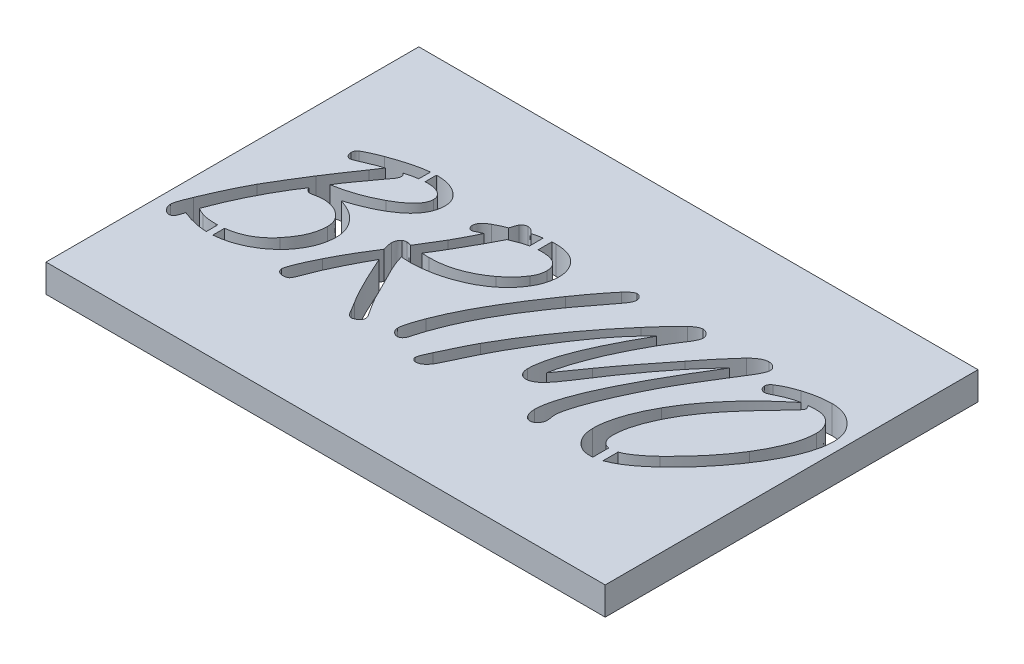
SolidWorks part; units mm, degrees
ref_plane "Front Plane" through (0, 0, 0) normal (0, 0, 1) x (1, 0, 0)
ref_plane "Top Plane" through (0, 0, 0) normal (0, 1, 0) x (1, 0, 0)
ref_plane "Right Plane" through (0, 0, 0) normal (1, 0, 0) x (0, 0, -1)
sketch "Sketch1" plane through (0, 0, 0) normal (0, 1, 0) x (1, 0, 0)
  line L1 (-15, -10) -> (15, -10)
  line L2 (-15, -10) -> (-15, 10)
  line L3 (-15, 10) -> (15, 10)
  line L4 (15, -10) -> (15, 10)
  line L5 (-15, -10) -> (15, 10) construction
  line L6 (-15, 10) -> (15, -10) construction
  point P0 (0, 0)
  dimension "D1" = 20
  dimension "D2" = 30
extrude "Boss-Extrude1" add sketch "Sketch1" along normal blind 1.5
sketch "Sketch2" plane through (0, 1.5, 0) normal (0, 1, 0) x (1, 0, 0)
  line L0 (12.5358, 3.7992) -> (12.0968, 3.7801)
  spline S0 degree 3 poles (-9.9324, 0.7721) (-9.7349, 0.705) (-9.3793, 0.5645) (-9.0629, 0.3483) (-8.9399, 0.2281) knots 0 0 0 0 0.54938 1 1 1 1
  spline S1 degree 3 poles (-8.9399, 0.2281) (-8.8499, 0.139) (-8.7235, -0.0008) (-8.5891, -0.2075) (-8.5077, -0.366) (-8.4446, -0.5298) (-8.3855, -0.7576) (-8.3678, -0.934) (-8.3674, -1.0525) knots 0 0 0 0 0.263598 0.389786 0.511629 0.633452 0.753743 1 1 1 1
  spline S2 degree 3 poles (-8.3674, -1.0525) (-8.3679, -1.1976) (-8.3862, -1.4147) (-8.4444, -1.6988) (-8.5079, -1.9082) (-8.5913, -2.1139) (-8.7218, -2.3919) (-8.8493, -2.5878) (-8.9418, -2.7149) knots 0 0 0 0 0.24321 0.364144 0.485641 0.609656 0.73611 1 1 1 1
  spline S3 degree 3 poles (-8.9418, -2.7149) (-9.1183, -2.9551) (-9.5377, -3.392) (-10.0436, -3.7249) (-10.316, -3.8601) knots 0 0 0 0 0.494771 1 1 1 1
  spline S4 degree 3 poles (-10.316, -3.8601) (-10.5882, -3.9961) (-11.1539, -4.2113) (-11.7551, -4.2809) (-12.051, -4.2819) knots 0 0 0 0 0.507133 1 1 1 1
  spline S5 degree 3 poles (-12.051, -4.2819) (-12.2925, -4.2818) (-12.803, -4.2161) (-13.2931, -4.0595) (-13.5435, -3.9555) knots 0 0 0 0 0.470723 1 1 1 1
  spline S6 degree 3 poles (-13.5435, -3.9555) (-13.5635, -4.0027) (-13.584, -4.0814) (-13.614, -4.1569) (-13.6198, -4.1865) knots 0 0 0 0 0.630096 1 1 1 1
  spline S7 degree 3 poles (-13.6198, -4.1865) (-13.6445, -4.2663) (-13.7016, -4.4114) (-13.838, -4.4919) (-13.9042, -4.488) knots 0 0 0 0 0.574548 1 1 1 1
  spline S8 degree 3 poles (-13.9042, -4.488) (-13.9704, -4.4895) (-14.1096, -4.4451) (-14.2083, -4.3383) (-14.2497, -4.2762) knots 0 0 0 0 0.465807 1 1 1 1
  spline S9 degree 2 poles (-14.2497, -4.2762) (-14.347, -4.1407) (-14.3528, -3.9746) knots 0 0 0 1 1 1
  spline S10 degree 3 poles (-14.3528, -3.9746) (-14.354, -3.926) (-14.3377, -3.8471) (-14.3104, -3.7313) (-14.275, -3.6224) (-14.2328, -3.497) (-14.1611, -3.2981) (-14.0922, -3.145) (-14.0493, -3.0356) knots 0 0 0 0 0.146035 0.243208 0.360183 0.492362 0.644092 1 1 1 1
  spline S11 degree 3 poles (-14.0493, -3.0356) (-13.951, -2.8027) (-13.8059, -2.4631) (-13.6103, -2.026) (-13.4703, -1.7282) (-13.3368, -1.4495) (-13.1732, -1.1148) (-13.046, -0.8771) (-12.9614, -0.7262) knots 0 0 0 0 0.296924 0.433728 0.562437 0.683432 0.796727 1 1 1 1
  spline S12 degree 3 poles (-12.9614, -0.7262) (-12.9019, -0.619) (-12.8008, -0.4453) (-12.6526, -0.1946) (-12.5099, 0.0354) (-12.353, 0.2979) (-12.1005, 0.7031) (-11.9023, 1.022) (-11.7628, 1.2435) knots 0 0 0 0 0.159441 0.261503 0.3789 0.511482 0.659407 1 1 1 1
  spline S13 degree 3 poles (-11.7628, 1.2435) (-11.6906, 1.3584) (-11.5739, 1.5364) (-11.4105, 1.7825) (-11.2727, 1.9894) (-11.1242, 2.2105) (-10.9038, 2.5333) (-10.7304, 2.7805) (-10.6138, 2.9517) knots 0 0 0 0 0.197743 0.310104 0.430435 0.560023 0.698104 1 1 1 1
  spline S14 degree 2 poles (-10.6138, 2.9517) (-10.4349, 3.2066) (-10.2702, 3.4709) knots 0 0 0 1 1 1
  spline S15 degree 3 poles (-10.2702, 3.4709) (-10.4018, 3.4327) (-10.6913, 3.3256) (-10.9761, 3.2067) (-11.1329, 3.1369) knots 0 0 0 0 0.443553 1 1 1 1
  spline S16 degree 3 poles (-11.1329, 3.1369) (-11.2484, 3.0843) (-11.4199, 3.0178) (-11.5936, 2.9522) (-11.6521, 2.946) knots 0 0 0 0 0.684268 1 1 1 1
  spline S17 degree 2 poles (-11.6521, 2.946) (-11.7629, 2.9529) (-11.8315, 3.0414) knots 0 0 0 1 1 1
  spline S18 degree 2 poles (-11.8315, 3.0414) (-11.9085, 3.1408) (-11.9078, 3.2666) knots 0 0 0 1 1 1
  spline S19 degree 3 poles (-11.9078, 3.2666) (-11.9068, 3.324) (-11.8898, 3.4402) (-11.8082, 3.5249) (-11.7628, 3.5529) knots 0 0 0 0 0.520839 1 1 1 1
  spline S20 degree 3 poles (-11.7628, 3.5529) (-11.6453, 3.6264) (-11.3377, 3.7844) (-11.0151, 3.9087) (-10.8218, 3.9824) knots 0 0 0 0 0.400792 1 1 1 1
  spline S21 degree 3 poles (-10.8218, 3.9824) (-10.5989, 4.0625) (-10.2751, 4.1829) (-9.8455, 4.3037) (-9.5525, 4.3827) (-9.2749, 4.4389) (-8.9413, 4.4946) (-8.6975, 4.5133) (-8.541, 4.513) knots 0 0 0 0 0.302191 0.439787 0.568842 0.688942 0.800686 1 1 1 1
  spline S22 degree 3 poles (-8.541, 4.513) (-8.3188, 4.5116) (-7.8963, 4.4723) (-7.5122, 4.2903) (-7.3558, 4.1732) knots 0 0 0 0 0.533748 1 1 1 1
  spline S23 degree 3 poles (-7.3558, 4.1732) (-7.2849, 4.1193) (-7.1843, 4.0329) (-7.0784, 3.8969) (-7.012, 3.7936) (-6.9619, 3.6837) (-6.9161, 3.528) (-6.9016, 3.4061) (-6.9015, 3.3239) knots 0 0 0 0 0.267458 0.393647 0.515248 0.634635 0.754006 1 1 1 1
  spline S24 degree 3 poles (-6.9015, 3.3239) (-6.9019, 3.1512) (-6.943, 2.8903) (-7.0819, 2.5662) (-7.2282, 2.3321) (-7.416, 2.108) (-7.7327, 1.8087) (-8.0162, 1.6207) (-8.2166, 1.5012) knots 0 0 0 0 0.219659 0.331396 0.446659 0.569712 0.702581 1 1 1 1
  spline S25 degree 3 poles (-8.2166, 1.5012) (-8.4812, 1.3441) (-9.0423, 1.0711) (-9.6282, 0.8568) (-9.9324, 0.7721) knots 0 0 0 0 0.49355 1 1 1 1
  spline S26 degree 3 poles (-10.9688, 1.2149) (-10.5802, 1.2808) (-9.8113, 1.4731) (-9.0867, 1.7947) (-8.7395, 1.9841) knots 0 0 0 0 0.499167 1 1 1 1
  spline S27 degree 3 poles (-8.7395, 1.9841) (-8.5538, 2.0831) (-8.2974, 2.2401) (-7.9959, 2.472) (-7.8223, 2.6395) (-7.6837, 2.8047) (-7.5579, 3.021) (-7.511, 3.1958) (-7.5123, 3.3105) knots 0 0 0 0 0.334645 0.477362 0.604033 0.717668 0.819211 1 1 1 1
  spline S28 degree 3 poles (-7.5123, 3.3105) (-7.5127, 3.4056) (-7.5684, 3.6137) (-7.7453, 3.7373) (-7.8368, 3.7877) knots 0 0 0 0 0.472721 1 1 1 1
  spline S29 degree 3 poles (-7.8368, 3.7877) (-7.9164, 3.8292) (-8.1115, 3.8909) (-8.3156, 3.9005) (-8.4284, 3.9022) knots 0 0 0 0 0.441874 1 1 1 1
  spline S30 degree 3 poles (-8.4284, 3.9022) (-8.6058, 3.9032) (-8.9873, 3.8621) (-9.3598, 3.7713) (-9.5564, 3.7114) knots 0 0 0 0 0.462913 1 1 1 1
  spline S31 degree 3 poles (-9.5564, 3.7114) (-9.5203, 3.6881) (-9.46, 3.629) (-9.4355, 3.548) (-9.4362, 3.509) knots 0 0 0 0 0.526905 1 1 1 1
  spline S32 degree 3 poles (-9.4362, 3.509) (-9.44, 3.4406) (-9.4955, 3.2764) (-9.6073, 3.1445) (-9.669, 3.0643) knots 0 0 0 0 0.400176 1 1 1 1
  spline S33 degree 3 poles (-9.669, 3.0643) (-9.7058, 3.0181) (-9.7984, 2.893) (-9.8901, 2.7673) (-9.9458, 2.6883) knots 0 0 0 0 0.37937 1 1 1 1
  spline S34 degree 3 poles (-9.9458, 2.6883) (-9.9661, 2.6605) (-9.9966, 2.6094) (-10.0499, 2.5374) (-10.1042, 2.4642) (-10.166, 2.3768) (-10.2692, 2.2363) (-10.3521, 2.1256) (-10.4096, 2.047) knots 0 0 0 0 0.130417 0.225441 0.339258 0.475767 0.631066 1 1 1 1
  spline S35 degree 3 poles (-10.4096, 2.047) (-10.5229, 1.8942) (-10.718, 1.6225) (-10.8969, 1.3398) (-10.9688, 1.2149) knots 0 0 0 0 0.569145 1 1 1 1
  spline S36 degree 3 poles (-13.3755, -3.3963) (-13.309, -3.4356) (-13.1926, -3.4898) (-13.0768, -3.5456) (-13.0282, -3.5624) knots 0 0 0 0 0.600478 1 1 1 1
  spline S37 degree 3 poles (-13.0282, -3.5624) (-12.9152, -3.6025) (-12.6518, -3.6608) (-12.3825, -3.6684) (-12.2342, -3.6712) knots 0 0 0 0 0.446321 1 1 1 1
  spline S38 degree 3 poles (-12.2342, -3.6712) (-11.9986, -3.6689) (-11.6488, -3.6432) (-11.2057, -3.5245) (-10.8972, -3.4069) (-10.6077, -3.2542) (-10.2422, -3.003) (-10.0039, -2.7645) (-9.8599, -2.5909) knots 0 0 0 0 0.262261 0.386546 0.508478 0.628294 0.749249 1 1 1 1
  spline S39 degree 3 poles (-9.8599, -2.5909) (-9.7394, -2.4469) (-9.5768, -2.2248) (-9.3945, -1.9167) (-9.2873, -1.6911) (-9.2043, -1.4662) (-9.126, -1.171) (-9.0988, -0.9457) (-9.1003, -0.7968) knots 0 0 0 0 0.283179 0.414403 0.539791 0.659455 0.77565 1 1 1 1
  spline S40 degree 3 poles (-9.1003, -0.7968) (-9.1009, -0.7011) (-9.117, -0.5583) (-9.179, -0.3799) (-9.2437, -0.2561) (-9.3234, -0.1386) (-9.4623, 0.0088) (-9.5882, 0.1003) (-9.6786, 0.1556) knots 0 0 0 0 0.245661 0.3649 0.482429 0.60331 0.728041 1 1 1 1
  spline S41 degree 3 poles (-9.6786, 0.1556) (-9.793, 0.2259) (-10.0547, 0.3291) (-10.3339, 0.3592) (-10.4783, 0.3598) knots 0 0 0 0 0.481057 1 1 1 1
  spline S42 degree 3 poles (-10.4783, 0.3598) (-10.5505, 0.3601) (-10.7236, 0.3426) (-10.894, 0.3084) (-10.9936, 0.2892) knots 0 0 0 0 0.415623 1 1 1 1
  spline S43 degree 2 poles (-10.9936, 0.2892) (-11.056, 0.2769) (-11.1196, 0.2759) knots 0 0 0 1 1 1
  spline S44 degree 3 poles (-11.1196, 0.2759) (-11.1774, 0.2719) (-11.2946, 0.3314) (-11.3691, 0.4367) (-11.3982, 0.5011) knots 0 0 0 0 0.439946 1 1 1 1
  spline S45 degree 3 poles (-11.3982, 0.5011) (-11.4981, 0.3605) (-11.6471, 0.1386) (-11.8397, -0.1762) (-11.9935, -0.4395) (-12.1545, -0.721) (-12.3754, -1.1358) (-12.5428, -1.4565) (-12.6522, -1.6786) knots 0 0 0 0 0.205495 0.318511 0.439849 0.568893 0.70494 1 1 1 1
  spline S46 degree 3 poles (-12.6522, -1.6786) (-12.7776, -1.9379) (-13.0389, -2.5023) (-13.2589, -3.0841) (-13.3755, -3.3963) knots 0 0 0 0 0.463574 1 1 1 1
  spline S47 degree 3 poles (-6.1877, -0.9457) (-6.33, -1.203) (-6.533, -1.5796) (-6.7863, -2.0714) (-6.9521, -2.4088) (-7.1013, -2.7256) (-7.2703, -3.1047) (-7.3829, -3.3812) (-7.4474, -3.5605) knots 0 0 0 0 0.303657 0.44176 0.571338 0.69184 0.803309 1 1 1 1
  spline S48 degree 3 poles (-7.4474, -3.5605) (-7.4779, -3.6449) (-7.5233, -3.7634) (-7.5816, -3.9106) (-7.6216, -3.9966) (-7.6517, -4.0697) (-7.688, -4.1338) (-7.7134, -4.1736) (-7.7318, -4.1922) knots 0 0 0 0 0.387425 0.547466 0.682625 0.796883 0.887789 1 1 1 1
  spline S49 degree 3 poles (-7.7318, -4.1922) (-7.7648, -4.2273) (-7.8637, -4.2692) (-7.9688, -4.283) (-8.0276, -4.2819) knots 0 0 0 0 0.444412 1 1 1 1
  spline S50 degree 3 poles (-8.0276, -4.2819) (-8.0774, -4.2829) (-8.1739, -4.2688) (-8.2553, -4.2149) (-8.2853, -4.1808) knots 0 0 0 0 0.525178 1 1 1 1
  spline S51 degree 2 poles (-8.2853, -4.1808) (-8.3613, -4.0988) (-8.3674, -3.988) knots 0 0 0 1 1 1
  spline S52 degree 3 poles (-8.3674, -3.988) (-8.3664, -3.9165) (-8.334, -3.7965) (-8.2754, -3.6182) (-8.2053, -3.4376) (-8.1152, -3.2267) (-7.9604, -2.882) (-7.8283, -2.6113) (-7.7337, -2.421) knots 0 0 0 0 0.125195 0.21875 0.331978 0.467572 0.624161 1 1 1 1
  spline S53 degree 3 poles (-7.7337, -2.421) (-7.5709, -2.0885) (-7.1843, -1.3876) (-6.7681, -0.704) (-6.5351, -0.3425) knots 0 0 0 0 0.462548 1 1 1 1
  spline S54 degree 3 poles (-6.5351, -0.3425) (-6.5647, -0.2466) (-6.6025, -0.0789) (-6.6314, 0.091) (-6.6305, 0.1632) knots 0 0 0 0 0.582415 1 1 1 1
  spline S55 degree 3 poles (-6.6305, 0.1632) (-6.6312, 0.239) (-6.602, 0.3888) (-6.5089, 0.51) (-6.4511, 0.5545) knots 0 0 0 0 0.510937 1 1 1 1
  spline S56 degree 2 poles (-6.4511, 0.5545) (-6.3635, 0.6197) (-6.2545, 0.6194) knots 0 0 0 1 1 1
  spline S57 degree 2 poles (-6.2545, 0.6194) (-6.1222, 0.6133) (-6.0026, 0.5545) knots 0 0 0 1 1 1
  spline S58 degree 3 poles (-6.0026, 0.5545) (-5.9746, 0.602) (-5.9223, 0.6861) (-5.8419, 0.8187) (-5.755, 0.9597) (-5.651, 1.1298) (-5.4764, 1.4113) (-5.3418, 1.6403) (-5.241, 1.7989) knots 0 0 0 0 0.113303 0.203721 0.318822 0.453891 0.613642 1 1 1 1
  spline S59 degree 3 poles (-5.241, 1.7989) (-5.1557, 1.9625) (-5.0255, 2.1882) (-4.8785, 2.4791) (-4.7852, 2.6509) (-4.7136, 2.7971) (-4.6454, 2.9327) (-4.6058, 3.0222) (-4.5883, 3.0739) knots 0 0 0 0 0.386157 0.545202 0.682224 0.79539 0.885924 1 1 1 1
  spline S60 degree 2 poles (-4.5883, 3.0739) (-4.7393, 3.0137) (-4.8822, 2.9365) knots 0 0 0 1 1 1
  spline S61 degree 2 poles (-4.8822, 2.9365) (-4.9704, 2.8893) (-5.0693, 2.8792) knots 0 0 0 1 1 1
  spline S62 degree 2 poles (-5.0693, 2.8792) (-5.168, 2.885) (-5.2201, 2.9708) knots 0 0 0 1 1 1
  spline S63 degree 2 poles (-5.2201, 2.9708) (-5.2693, 3.0444) (-5.2678, 3.133) knots 0 0 0 1 1 1
  spline S64 degree 3 poles (-5.2678, 3.133) (-5.2665, 3.1866) (-5.2538, 3.269) (-5.2036, 3.3683) (-5.1534, 3.442) (-5.0873, 3.5127) (-4.9756, 3.6078) (-4.877, 3.6671) (-4.8078, 3.7056) knots 0 0 0 0 0.209364 0.316672 0.430565 0.55486 0.691692 1 1 1 1
  spline S65 degree 2 poles (-4.8078, 3.7056) (-4.5026, 3.8755) (-4.176, 3.9996) knots 0 0 0 1 1 1
  spline S66 degree 3 poles (-4.176, 3.9996) (-4.1545, 4.0862) (-4.1044, 4.2198) (-4.059, 4.3557) (-4.031, 4.4023) knots 0 0 0 0 0.62241 1 1 1 1
  spline S67 degree 3 poles (-4.031, 4.4023) (-4.0022, 4.456) (-3.9133, 4.553) (-3.7844, 4.5777) (-3.7218, 4.5779) knots 0 0 0 0 0.492095 1 1 1 1
  spline S68 degree 3 poles (-3.7218, 4.5779) (-3.6454, 4.5787) (-3.4805, 4.5304) (-3.3677, 4.4011) (-3.3172, 4.3297) knots 0 0 0 0 0.46182 1 1 1 1
  spline S69 degree 3 poles (-3.3172, 4.3297) (-3.1152, 4.387) (-2.7292, 4.4766) (-2.3345, 4.5129) (-2.1491, 4.513) knots 0 0 0 0 0.531298 1 1 1 1
  spline S70 degree 3 poles (-2.1491, 4.513) (-2.0237, 4.5156) (-1.8419, 4.5002) (-1.6081, 4.4575) (-1.4508, 4.4089) (-1.3035, 4.3513) (-1.1285, 4.2495) (-1.0079, 4.1597) (-0.9409, 4.0854) knots 0 0 0 0 0.284878 0.414697 0.540253 0.65914 0.773942 1 1 1 1
  spline S71 degree 3 poles (-0.9409, 4.0854) (-0.8145, 3.9556) (-0.61, 3.6428) (-0.55, 3.2744) (-0.5497, 3.0911) knots 0 0 0 0 0.496609 1 1 1 1
  spline S72 degree 3 poles (-0.5497, 3.0911) (-0.5525, 2.9332) (-0.5727, 2.6947) (-0.6598, 2.3879) (-0.7453, 2.159) (-0.8583, 1.934) (-1.0486, 1.6339) (-1.2173, 1.4207) (-1.3456, 1.2874) knots 0 0 0 0 0.234943 0.352534 0.472741 0.597393 0.72559 1 1 1 1
  spline S73 degree 3 poles (-1.3456, 1.2874) (-1.4703, 1.1527) (-1.6774, 0.9674) (-1.9746, 0.7414) (-2.2174, 0.5851) (-2.474, 0.4376) (-2.8456, 0.2582) (-3.1362, 0.1396) (-3.3382, 0.0735) knots 0 0 0 0 0.233458 0.353169 0.474931 0.60081 0.729765 1 1 1 1
  spline S74 degree 3 poles (-3.3382, 0.0735) (-3.647, -0.0308) (-4.2677, -0.1928) (-4.9067, -0.2503) (-5.2201, -0.2509) knots 0 0 0 0 0.509986 1 1 1 1
  spline S75 degree 3 poles (-5.2201, -0.2509) (-5.2869, -0.25) (-5.4479, -0.2448) (-5.6088, -0.2367) (-5.7029, -0.2318) knots 0 0 0 0 0.414852 1 1 1 1
  spline S76 degree 2 poles (-5.7029, -0.2318) (-5.5875, -0.64) (-5.4071, -1.0239) knots 0 0 0 1 1 1
  spline S77 degree 3 poles (-5.4071, -1.0239) (-5.3475, -1.1433) (-5.2513, -1.3296) (-5.1198, -1.5906) (-5.0088, -1.8128) (-4.8896, -2.0525) (-4.7088, -2.4052) (-4.5738, -2.6807) (-4.4795, -2.8695) knots 0 0 0 0 0.193804 0.304548 0.424382 0.554546 0.69339 1 1 1 1
  spline S78 degree 3 poles (-4.4795, -2.8695) (-4.4059, -3.0003) (-4.2235, -3.3079) (-4.0278, -3.6073) (-3.9127, -3.7799) knots 0 0 0 0 0.419594 1 1 1 1
  spline S79 degree 2 poles (-3.9127, -3.7799) (-3.8179, -3.9082) (-3.8077, -4.0662) knots 0 0 0 1 1 1
  spline S80 degree 3 poles (-3.8077, -4.0662) (-3.8068, -4.1097) (-3.8433, -4.2026) (-3.9158, -4.2703) (-3.9604, -4.301) knots 0 0 0 0 0.439347 1 1 1 1
  spline S81 degree 3 poles (-3.9604, -4.301) (-4.0053, -4.3345) (-4.0939, -4.3741) (-4.1864, -4.4068) (-4.2295, -4.4041) knots 0 0 0 0 0.568772 1 1 1 1
  spline S82 degree 3 poles (-4.2295, -4.4041) (-4.3025, -4.4014) (-4.4538, -4.2832) (-4.5426, -4.1207) (-4.5959, -4.0185) knots 0 0 0 0 0.374194 1 1 1 1
  spline S83 degree 2 poles (-4.5959, -4.0185) (-4.7159, -3.8173) (-4.8383, -3.6177) knots 0 0 0 1 1 1
  spline S84 degree 3 poles (-4.8383, -3.6177) (-4.937, -3.4624) (-5.0891, -3.2122) (-5.2827, -2.8491) (-5.4479, -2.5315) (-5.6205, -2.1813) (-5.8723, -1.6508) (-6.059, -1.234) (-6.1877, -0.9457) knots 0 0 0 0 0.184322 0.292919 0.412015 0.54278 0.683829 1 1 1 1
  spline S85 degree 3 poles (-5.3327, 0.4953) (-5.2557, 0.4902) (-5.124, 0.4884) (-4.9924, 0.4799) (-4.9376, 0.482) knots 0 0 0 0 0.584631 1 1 1 1
  spline S86 degree 3 poles (-4.9376, 0.482) (-4.7021, 0.4846) (-4.3485, 0.5086) (-3.8885, 0.608) (-3.5492, 0.7058) (-3.2175, 0.8379) (-2.777, 1.0517) (-2.4627, 1.2512) (-2.2617, 1.4) knots 0 0 0 0 0.245681 0.367674 0.490007 0.613272 0.739318 1 1 1 1
  spline S87 degree 3 poles (-2.2617, 1.4) (-2.0834, 1.5301) (-1.7572, 1.8167) (-1.4892, 2.1582) (-1.3761, 2.3372) knots 0 0 0 0 0.510601 1 1 1 1
  spline S88 degree 3 poles (-1.3761, 2.3372) (-1.309, 2.4424) (-1.1951, 2.6649) (-1.1609, 2.9127) (-1.1604, 3.0338) knots 0 0 0 0 0.507982 1 1 1 1
  spline S89 degree 3 poles (-1.1604, 3.0338) (-1.1581, 3.1453) (-1.1873, 3.3097) (-1.3007, 3.494) (-1.4198, 3.6001) (-1.5695, 3.6836) (-1.8293, 3.7659) (-2.0468, 3.7791) (-2.1987, 3.7801) knots 0 0 0 0 0.230322 0.334118 0.440956 0.555574 0.685495 1 1 1 1
  spline S90 degree 3 poles (-2.1987, 3.7801) (-2.3567, 3.7808) (-2.679, 3.7523) (-2.992, 3.6701) (-3.1473, 3.6159) knots 0 0 0 0 0.489735 1 1 1 1
  spline S91 degree 3 poles (-3.1473, 3.6159) (-3.2236, 3.5913) (-3.4009, 3.5205) (-3.5783, 3.4503) (-3.6798, 3.406) knots 0 0 0 0 0.419901 1 1 1 1
  spline S92 degree 3 poles (-3.6798, 3.406) (-3.7248, 3.3118) (-3.798, 3.1632) (-3.9075, 2.9587) (-4.0011, 2.7822) (-4.1038, 2.5918) (-4.2171, 2.3872) (-4.3387, 2.1681) (-4.468, 1.9397) (-4.5987, 1.7122) (-4.7246, 1.4945) (-4.843, 1.2922) (-4.9539, 1.1043) (-5.0585, 0.9314) (-5.1828, 0.7291) (-5.2732, 0.5853) (-5.3327, 0.4953) knots 0 0 0 0 0.093552 0.148371 0.207782 0.272559 0.342203 0.417217 0.497105 0.577275 0.652356 0.72235 0.787257 0.847862 0.903387 1 1 1 1
  spline S93 degree 2 poles (2.3228, 4.3908) (2.4521, 4.3827) (2.5365, 4.282) knots 0 0 0 1 1 1
  spline S94 degree 2 poles (2.5365, 4.282) (2.6222, 4.1931) (2.6262, 4.0702) knots 0 0 0 1 1 1
  spline S95 degree 3 poles (2.6262, 4.0702) (2.6248, 4.0051) (2.5782, 3.8503) (2.4909, 3.7155) (2.4411, 3.635) knots 0 0 0 0 0.404557 1 1 1 1
  spline S96 degree 3 poles (2.4411, 3.635) (2.4174, 3.5988) (2.3698, 3.5377) (2.2991, 3.4412) (2.2219, 3.3401) (2.1316, 3.2182) (1.9773, 3.0185) (1.8537, 2.8595) (1.7674, 2.7456) knots 0 0 0 0 0.116341 0.208022 0.321596 0.458432 0.615802 1 1 1 1
  spline S97 degree 3 poles (1.7674, 2.7456) (1.545, 2.46) (1.2212, 2.033) (0.8101, 1.4596) (0.5221, 1.0401) (0.2495, 0.6252) (-0.0115, 0.2177) (-0.2526, -0.187) (-0.4807, -0.5851) (-0.6946, -0.977) (-0.8919, -1.3654) (-1.0718, -1.7488) (-1.2419, -2.1247) (-1.3919, -2.4971) (-1.57, -2.9798) (-1.6888, -3.3415) (-1.754, -3.5834) knots 0 0 0 0 0.149039 0.220561 0.290451 0.35852 0.424933 0.489661 0.552427 0.613842 0.673465 0.731695 0.788208 0.843315 0.896933 1 1 1 1
  spline S98 degree 3 poles (-1.754, -3.5834) (-1.7645, -3.652) (-1.7946, -3.7449) (-1.8434, -3.8588) (-1.8892, -3.9226) (-1.9372, -3.9758) (-2.0152, -4.0233) (-2.0817, -4.0369) (-2.1262, -4.0376) knots 0 0 0 0 0.323178 0.457887 0.577798 0.689538 0.791288 1 1 1 1
  spline S99 degree 3 poles (-2.1262, -4.0376) (-2.1761, -4.0407) (-2.2758, -4.0084) (-2.3595, -3.9466) (-2.3934, -3.904) knots 0 0 0 0 0.476203 1 1 1 1
  spline S100 degree 3 poles (-2.3934, -3.904) (-2.4275, -3.8657) (-2.4847, -3.7793) (-2.5032, -3.6773) (-2.5041, -3.6273) knots 0 0 0 0 0.506247 1 1 1 1
  spline S101 degree 3 poles (-2.5041, -3.6273) (-2.5029, -3.5625) (-2.4889, -3.4569) (-2.4578, -3.3052) (-2.4221, -3.1655) (-2.3719, -3.0101) (-2.2962, -2.7653) (-2.2243, -2.5761) (-2.1739, -2.4439) knots 0 0 0 0 0.157378 0.258461 0.376716 0.507925 0.655757 1 1 1 1
  spline S102 degree 3 poles (-2.1739, -2.4439) (-2.0378, -2.0885) (-1.8032, -1.5473) (-1.4362, -0.8234) (-1.1146, -0.2399) (-0.7574, 0.3695) (-0.2154, 1.2369) (0.2265, 1.889) (0.5363, 2.3295) knots 0 0 0 0 0.207458 0.321318 0.442402 0.570662 0.70637 1 1 1 1
  spline S103 degree 3 poles (0.5363, 2.3295) (0.6617, 2.5085) (0.8444, 2.7691) (1.0898, 3.0987) (1.2546, 3.3233) (1.4138, 3.5271) (1.6037, 3.7662) (1.7435, 3.9352) (1.8361, 4.0396) knots 0 0 0 0 0.305095 0.444183 0.573676 0.693947 0.80519 1 1 1 1
  spline S104 degree 3 poles (1.8361, 4.0396) (1.9225, 4.1363) (2.0668, 4.2788) (2.245, 4.3875) (2.3228, 4.3908) knots 0 0 0 0 0.632298 1 1 1 1
  spline S105 degree 3 poles (3.5748, -1.7167) (3.6252, -1.6503) (3.7068, -1.535) (3.8289, -1.3651) (3.9481, -1.1979) (4.0846, -1.0043) (4.3027, -0.6933) (4.4788, -0.4499) (4.5978, -0.2757) knots 0 0 0 0 0.141499 0.239802 0.355179 0.490018 0.641932 1 1 1 1
  spline S106 degree 3 poles (4.5978, -0.2757) (4.7257, -0.0932) (4.9325, 0.1922) (5.2293, 0.5877) (5.486, 0.9264) (5.7671, 1.2916) (6.1901, 1.8324) (6.5197, 2.2515) (6.7508, 2.5376) knots 0 0 0 0 0.188686 0.298364 0.41871 0.548545 0.688631 1 1 1 1
  spline S107 degree 3 poles (6.7508, 2.5376) (7.0065, 2.869) (7.4921, 3.4753) (8.0021, 4.0612) (8.2452, 4.324) knots 0 0 0 0 0.539038 1 1 1 1
  spline S108 degree 3 poles (8.2452, 4.324) (8.3712, 4.4467) (8.6051, 4.6465) (8.8954, 4.7575) (9.0258, 4.7573) knots 0 0 0 0 0.579561 1 1 1 1
  spline S109 degree 3 poles (9.0258, 4.7573) (9.0865, 4.7571) (9.2065, 4.74) (9.3086, 4.6746) (9.3503, 4.6351) knots 0 0 0 0 0.51453 1 1 1 1
  spline S110 degree 3 poles (9.3503, 4.6351) (9.3862, 4.6056) (9.4499, 4.5323) (9.4656, 4.4368) (9.4667, 4.3908) knots 0 0 0 0 0.502535 1 1 1 1
  spline S111 degree 3 poles (9.4667, 4.3908) (9.4653, 4.2922) (9.3805, 4.0533) (9.2589, 3.8341) (9.1766, 3.7037) knots 0 0 0 0 0.38693 1 1 1 1
  spline S112 degree 3 poles (9.1766, 3.7037) (9.1593, 3.6715) (9.1208, 3.6147) (9.0654, 3.52) (9, 3.4153) (8.9198, 3.2879) (8.7859, 3.0706) (8.676, 2.8976) (8.5983, 2.7742) knots 0 0 0 0 0.100186 0.187791 0.300522 0.438384 0.600456 1 1 1 1
  spline S113 degree 3 poles (8.5983, 2.7742) (8.4551, 2.5425) (8.2495, 2.2076) (7.9892, 1.7789) (7.8225, 1.4966) (7.6742, 1.2422) (7.5112, 0.957) (7.3995, 0.7561) (7.3348, 0.6289) knots 0 0 0 0 0.328237 0.473354 0.604277 0.723114 0.828163 1 1 1 1
  spline S114 degree 3 poles (7.3348, 0.6289) (7.1908, 0.3476) (6.9804, -0.0652) (6.7218, -0.6107) (6.549, -0.9944) (6.3873, -1.3598) (6.2023, -1.8149) (6.0733, -2.1489) (6.0007, -2.3695) knots 0 0 0 0 0.28871 0.423089 0.551296 0.673071 0.78799 1 1 1 1
  spline S115 degree 3 poles (6.0007, -2.3695) (5.9648, -2.4847) (5.909, -2.6491) (5.8501, -2.8632) (5.8164, -3.0048) (5.7862, -3.1341) (5.763, -3.2824) (5.7526, -3.3877) (5.7526, -3.4536) knots 0 0 0 0 0.324552 0.466455 0.596707 0.715802 0.823211 1 1 1 1
  spline S116 degree 2 poles (5.7526, -3.4536) (5.753, -3.5344) (5.7678, -3.6139) knots 0 0 0 1 1 1
  spline S117 degree 3 poles (5.7678, -3.6139) (5.7754, -3.6802) (5.7925, -3.7782) (5.8011, -3.8772) (5.8022, -3.9097) knots 0 0 0 0 0.672229 1 1 1 1
  spline S118 degree 3 poles (5.8022, -3.9097) (5.8012, -3.9708) (5.7773, -4.101) (5.6978, -4.207) (5.6533, -4.2571) knots 0 0 0 0 0.475441 1 1 1 1
  spline S119 degree 3 poles (5.6533, -4.2571) (5.6146, -4.301) (5.5278, -4.3784) (5.4143, -4.4029) (5.3613, -4.4041) knots 0 0 0 0 0.526092 1 1 1 1
  spline S120 degree 3 poles (5.3613, -4.4041) (5.299, -4.4061) (5.1692, -4.3601) (5.0813, -4.2547) (5.0483, -4.1922) knots 0 0 0 0 0.463853 1 1 1 1
  spline S121 degree 3 poles (5.0483, -4.1922) (5.0124, -4.132) (4.9573, -3.9844) (4.9469, -3.8273) (4.9471, -3.7418) knots 0 0 0 0 0.449011 1 1 1 1
  spline S122 degree 3 poles (4.9471, -3.7418) (4.9489, -3.5707) (4.9791, -3.2996) (5.0638, -2.9248) (5.1535, -2.6003) (5.2709, -2.249) (5.4155, -1.871) (5.5834, -1.4649) (5.7769, -1.0309) (5.9963, -0.5695) (6.2433, -0.0814) (6.5146, 0.4348) (6.8127, 0.9777) (7.135, 1.549) (7.6147, 2.3661) (7.9906, 2.9909) (8.2547, 3.4136) knots 0 0 0 0 0.064535 0.10266 0.145036 0.19161 0.24248 0.29785 0.357544 0.421917 0.490791 0.564085 0.642146 0.724664 0.811775 1 1 1 1
  spline S123 degree 3 poles (8.2547, 3.4136) (7.9603, 3.1124) (7.5215, 2.6291) (6.9493, 1.9367) (6.495, 1.3567) (6.0321, 0.7288) (5.3786, -0.1892) (4.9021, -0.9139) (4.5807, -1.4114) knots 0 0 0 0 0.20798 0.322231 0.443538 0.571796 0.70745 1 1 1 1
  spline S124 degree 3 poles (4.5807, -1.4114) (4.5117, -1.5167) (4.411, -1.6685) (4.2727, -1.8563) (4.1796, -1.9794) (4.0897, -2.0876) (3.9841, -2.2091) (3.9028, -2.2892) (3.8478, -2.3351) knots 0 0 0 0 0.319607 0.461633 0.591714 0.710941 0.818427 1 1 1 1
  spline S125 degree 3 poles (3.8478, -2.3351) (3.7647, -2.4036) (3.6028, -2.5214) (3.4082, -2.5713) (3.3191, -2.5718) knots 0 0 0 0 0.54989 1 1 1 1
  spline S126 degree 3 poles (3.3191, -2.5718) (3.2449, -2.5711) (3.0914, -2.5429) (2.985, -2.428) (2.9507, -2.3638) knots 0 0 0 0 0.506516 1 1 1 1
  spline S127 degree 2 poles (2.9507, -2.3638) (2.8698, -2.2128) (2.8706, -2.0412) knots 0 0 0 1 1 1
  spline S128 degree 3 poles (2.8706, -2.0412) (2.8705, -1.9) (2.8886, -1.6807) (2.9382, -1.3809) (2.9922, -1.1339) (3.0617, -0.8732) (3.1434, -0.5971) (3.2432, -0.3078) (3.3584, -0.0047) (3.4861, 0.3135) (3.6314, 0.6447) (3.7923, 0.9896) (3.9657, 1.35) (4.1578, 1.7228) (4.4342, 2.2543) (4.6619, 2.653) (4.8154, 2.925) knots 0 0 0 0 0.078657 0.122518 0.16935 0.219605 0.272923 0.329918 0.390211 0.45372 0.521084 0.591878 0.665979 0.744044 0.825771 1 1 1 1
  spline S129 degree 3 poles (4.8154, 2.925) (4.5744, 2.6998) (4.0989, 2.212) (3.6711, 1.682) (3.4603, 1.4019) knots 0 0 0 0 0.484816 1 1 1 1
  spline S130 degree 3 poles (3.4603, 1.4019) (3.0698, 0.8754) (2.3318, -0.1965) (1.6642, -1.3136) (1.3532, -1.879) knots 0 0 0 0 0.503988 1 1 1 1
  spline S131 degree 3 poles (1.3532, -1.879) (1.2755, -2.0246) (1.1526, -2.2497) (0.9933, -2.5655) (0.8637, -2.8274) (0.726, -3.1056) (0.5302, -3.5101) (0.3848, -3.8238) (0.2844, -4.0376) knots 0 0 0 0 0.205562 0.319294 0.440464 0.569431 0.705847 1 1 1 1
  spline S132 degree 3 poles (0.2844, -4.0376) (0.2361, -4.1416) (0.1616, -4.2883) (0.042, -4.4593) (-0.0486, -4.5573) (-0.1401, -4.6362) (-0.2674, -4.7077) (-0.3718, -4.7319) (-0.4409, -4.7323) knots 0 0 0 0 0.325035 0.46453 0.589491 0.70207 0.805323 1 1 1 1
  spline S133 degree 2 poles (-0.4409, -4.7323) (-0.5477, -4.7306) (-0.6165, -4.6484) knots 0 0 0 1 1 1
  spline S134 degree 2 poles (-0.6165, -4.6484) (-0.6729, -4.589) (-0.6718, -4.5071) knots 0 0 0 1 1 1
  spline S135 degree 3 poles (-0.6718, -4.5071) (-0.6716, -4.4769) (-0.6568, -4.4269) (-0.6347, -4.3505) (-0.6055, -4.2738) (-0.5694, -4.1831) (-0.5025, -4.0376) (-0.4531, -3.9197) (-0.4123, -3.8391) knots 0 0 0 0 0.124733 0.216248 0.332117 0.466663 0.623497 1 1 1 1
  spline S136 degree 3 poles (-0.4123, -3.8391) (-0.3282, -3.6519) (-0.1987, -3.3857) (-0.0381, -3.0411) (0.0729, -2.816) (0.173, -2.6099) (0.2958, -2.3806) (0.3759, -2.2147) (0.4352, -2.1156) knots 0 0 0 0 0.320471 0.462249 0.59378 0.712419 0.819964 1 1 1 1
  spline S137 degree 3 poles (0.4352, -2.1156) (0.6869, -1.6683) (1.0803, -1.0062) (1.641, -0.1456) (2.0781, 0.4902) (2.5326, 1.1163) (3.1617, 1.9398) (3.6595, 2.5386) (4.0004, 2.9307) knots 0 0 0 0 0.248788 0.373149 0.497772 0.622737 0.748123 1 1 1 1
  spline S138 degree 3 poles (4.0004, 2.9307) (4.1301, 3.0833) (4.322, 3.2962) (4.5641, 3.5681) (4.7234, 3.7366) (4.8623, 3.8871) (5.0155, 4.0438) (5.1218, 4.1515) (5.1914, 4.2114) knots 0 0 0 0 0.343163 0.491462 0.624213 0.74075 0.842579 1 1 1 1
  spline S139 degree 3 poles (5.1914, 4.2114) (5.2878, 4.2929) (5.4513, 4.436) (5.657, 4.5102) (5.7449, 4.513) knots 0 0 0 0 0.593682 1 1 1 1
  spline S140 degree 2 poles (5.7449, 4.513) (5.8993, 4.5059) (6.0121, 4.3985) knots 0 0 0 1 1 1
  spline S141 degree 3 poles (6.0121, 4.3985) (6.0591, 4.3585) (6.1411, 4.268) (6.1691, 4.1491) (6.1686, 4.0931) knots 0 0 0 0 0.526499 1 1 1 1
  spline S142 degree 3 poles (6.1686, 4.0931) (6.1665, 4.003) (6.0794, 3.7829) (5.9609, 3.5819) (5.8785, 3.4613) knots 0 0 0 0 0.378239 1 1 1 1
  spline S143 degree 3 poles (5.8785, 3.4613) (5.5938, 3.0315) (5.0446, 2.1177) (4.5747, 1.1608) (4.3497, 0.6595) knots 0 0 0 0 0.484051 1 1 1 1
  spline S144 degree 3 poles (4.3497, 0.6595) (4.2535, 0.437) (4.1221, 0.1072) (3.9586, -0.3248) (3.856, -0.6289) (3.7652, -0.9194) (3.6679, -1.2794) (3.6036, -1.5435) (3.5748, -1.7167) knots 0 0 0 0 0.290271 0.425315 0.553286 0.674537 0.789903 1 1 1 1
  spline S145 degree 3 poles (11.7723, 3.7266) (11.5819, 3.6946) (11.1653, 3.5738) (10.7734, 3.3885) (10.5603, 3.28) knots 0 0 0 0 0.446223 1 1 1 1
  spline S146 degree 2 poles (10.5603, 3.28) (10.4481, 3.2151) (10.3199, 3.2037) knots 0 0 0 1 1 1
  spline S147 degree 2 poles (10.3199, 3.2037) (10.2075, 3.2126) (10.1271, 3.2934) knots 0 0 0 1 1 1
  spline S148 degree 2 poles (10.1271, 3.2934) (10.0335, 3.391) (10.0317, 3.5262) knots 0 0 0 1 1 1
  spline S149 degree 3 poles (10.0317, 3.5262) (10.0319, 3.5776) (10.0676, 3.6877) (10.1551, 3.7628) (10.2034, 3.7972) knots 0 0 0 0 0.45902 1 1 1 1
  spline S150 degree 3 poles (10.2034, 3.7972) (10.3536, 3.895) (10.6873, 4.0842) (11.0495, 4.2107) (11.2417, 4.2744) knots 0 0 0 0 0.469139 1 1 1 1
  spline S151 degree 3 poles (11.2417, 4.2744) (11.4789, 4.3505) (11.9417, 4.469) (12.4176, 4.5117) (12.6445, 4.513) knots 0 0 0 0 0.52343 1 1 1 1
  spline S152 degree 3 poles (12.6445, 4.513) (12.7776, 4.5149) (12.9735, 4.4971) (13.2243, 4.4393) (13.4008, 4.3838) (13.5653, 4.3055) (13.7747, 4.1828) (13.9145, 4.0641) (13.9997, 3.9767) knots 0 0 0 0 0.266205 0.391632 0.514867 0.635657 0.755564 1 1 1 1
  spline S153 degree 3 poles (13.9997, 3.9767) (14.076, 3.899) (14.1816, 3.7743) (14.2917, 3.5891) (14.3599, 3.4443) (14.4105, 3.2923) (14.4601, 3.0772) (14.4752, 2.9104) (14.4749, 2.7971) knots 0 0 0 0 0.250353 0.372867 0.493777 0.617124 0.740091 1 1 1 1
  spline S154 degree 3 poles (14.4749, 2.7971) (14.4756, 2.5913) (14.4385, 2.274) (14.3353, 1.8472) (14.2262, 1.5013) (14.0838, 1.1402) (13.8429, 0.6225) (13.6279, 0.2361) (13.471, -0.0238) knots 0 0 0 0 0.203603 0.315031 0.434616 0.562523 0.699274 1 1 1 1
  spline S155 degree 3 poles (13.471, -0.0238) (13.2896, -0.318) (13.0053, -0.7516) (12.5911, -1.3048) (12.267, -1.7089) (11.929, -2.1029) (11.4566, -2.6134) (11.0811, -2.9772) (10.8218, -3.2112) knots 0 0 0 0 0.249402 0.373687 0.498405 0.623055 0.748094 1 1 1 1
  spline S156 degree 3 poles (10.8218, -3.2112) (10.6176, -3.3945) (10.3124, -3.6484) (9.8939, -3.936) (9.6048, -4.1069) (9.3256, -4.2367) (8.9823, -4.3613) (8.721, -4.4024) (8.5525, -4.4041) knots 0 0 0 0 0.314834 0.454469 0.581982 0.699492 0.807023 1 1 1 1
  spline S157 degree 3 poles (8.5525, -4.4041) (8.4631, -4.4048) (8.3318, -4.3885) (8.1636, -4.3404) (8.0476, -4.2859) (7.9371, -4.2185) (7.7968, -4.1059) (7.7053, -4.0029) (7.6516, -3.9269) knots 0 0 0 0 0.252046 0.372097 0.492792 0.613072 0.737202 1 1 1 1
  spline S158 degree 3 poles (7.6516, -3.9269) (7.5665, -3.8039) (7.4272, -3.5261) (7.3924, -3.2176) (7.3901, -3.0623) knots 0 0 0 0 0.490165 1 1 1 1
  spline S159 degree 3 poles (7.3901, -3.0623) (7.3897, -2.8518) (7.4203, -2.5286) (7.514, -2.0957) (7.6115, -1.7512) (7.7388, -1.3953) (7.9518, -0.8906) (8.1437, -0.5142) (8.2853, -0.2624) knots 0 0 0 0 0.212421 0.326727 0.44694 0.573758 0.708251 1 1 1 1
  spline S160 degree 3 poles (8.2853, -0.2624) (8.4903, 0.0978) (8.8245, 0.6309) (9.3364, 1.3053) (9.754, 1.8109) (10.2094, 2.3041) (10.8687, 2.9607) (11.4008, 3.4267) (11.7723, 3.7266) knots 0 0 0 0 0.233341 0.353523 0.476359 0.602322 0.731212 1 1 1 1
  spline S161 degree 3 poles (12.0968, 3.7801) (12.1295, 3.7434) (12.1829, 3.6754) (12.2103, 3.593) (12.2113, 3.5568) knots 0 0 0 0 0.579121 1 1 1 1
  spline S162 degree 3 poles (12.2113, 3.5568) (12.2088, 3.5348) (12.192, 3.4985) (12.1573, 3.4481) (12.1193, 3.3935) (12.0671, 3.3315) (11.9766, 3.2279) (11.9037, 3.1449) (11.8487, 3.0891) knots 0 0 0 0 0.110012 0.197914 0.308066 0.44456 0.605674 1 1 1 1
  spline S163 degree 3 poles (11.8487, 3.0891) (11.6145, 2.8518) (11.277, 2.5019) (10.8517, 2.0373) (10.5659, 1.7148) (10.3017, 1.41) (9.9948, 1.0375) (9.7846, 0.7598) (9.6538, 0.5793) knots 0 0 0 0 0.299733 0.43696 0.566193 0.687033 0.799584 1 1 1 1
  spline S164 degree 3 poles (9.6538, 0.5793) (9.4178, 0.2458) (8.9858, -0.4189) (8.659, -1.1411) (8.5219, -1.4972) knots 0 0 0 0 0.517149 1 1 1 1
  spline S165 degree 3 poles (8.5219, -1.4972) (8.4401, -1.7296) (8.2999, -2.1667) (8.2462, -2.6229) (8.2452, -2.8333) knots 0 0 0 0 0.540007 1 1 1 1
  spline S166 degree 3 poles (8.2452, -2.8333) (8.2452, -2.9217) (8.2617, -3.0895) (8.3245, -3.2463) (8.3674, -3.3123) knots 0 0 0 0 0.530501 1 1 1 1
  spline S167 degree 3 poles (8.3674, -3.3123) (8.4143, -3.3861) (8.548, -3.5136) (8.7289, -3.5493) (8.8178, -3.549) knots 0 0 0 0 0.49499 1 1 1 1
  spline S168 degree 3 poles (8.8178, -3.549) (8.9344, -3.5499) (9.1146, -3.5075) (9.357, -3.4097) (9.5591, -3.297) (9.7765, -3.1569) (10.0965, -2.9131) (10.3358, -2.7057) (10.4955, -2.5527) knots 0 0 0 0 0.174337 0.276799 0.393591 0.522685 0.666625 1 1 1 1
  spline S169 degree 3 poles (10.4955, -2.5527) (10.7117, -2.344) (11.0283, -2.0296) (11.4257, -1.5935) (11.7047, -1.2666) (11.9703, -0.9373) (12.2966, -0.495) (12.5282, -0.1574) (12.6694, 0.0735) knots 0 0 0 0 0.263745 0.391402 0.517729 0.640851 0.762567 1 1 1 1
  spline S170 degree 3 poles (12.6694, 0.0735) (12.8176, 0.316) (13.0239, 0.675) (13.247, 1.161) (13.3848, 1.4973) (13.4879, 1.8219) (13.5864, 2.2219) (13.6187, 2.5203) (13.6198, 2.7132) knots 0 0 0 0 0.300487 0.436767 0.564994 0.684285 0.796321 1 1 1 1
  spline S171 degree 3 poles (13.6198, 2.7132) (13.6225, 2.8719) (13.5665, 3.1858) (13.3832, 3.4466) (13.2706, 3.5491) knots 0 0 0 0 0.511004 1 1 1 1
  spline S172 degree 3 poles (13.2706, 3.5491) (13.1795, 3.6341) (12.9437, 3.766) (12.6762, 3.8001) (12.5358, 3.7992) knots 0 0 0 0 0.468065 1 1 1 1
extrude "Cut-Extrude1" cut sketch "Sketch2" against normal up to next
sketch "Sketch3" plane through (0, 1.5, 0) normal (0, 1, 0) x (1, 0, 0)
  line L1 (-12.118, -4.8235) -> (-11.7795, -4.8235)
  line L2 (-12.118, -4.8235) -> (-12.118, -2.9956)
  line L3 (-12.118, -2.9956) -> (-11.7795, -2.9956)
  line L4 (-11.7795, -4.8235) -> (-11.7795, -2.9956)
  line L5 (-8.8685, 5.1958) -> (-8.5638, 5.1958)
  line L6 (-8.8685, 5.1958) -> (-8.8685, 3.5372)
  line L7 (-8.8685, 3.5372) -> (-8.5638, 3.5372)
  line L8 (-8.5638, 5.1958) -> (-8.5638, 3.5372)
  line L9 (-2.7756, 4.7896) -> (-2.3694, 4.7896)
  line L10 (-2.7756, 4.7896) -> (-2.7756, 3.1649)
  line L11 (-2.7756, 3.1649) -> (-2.3694, 3.1649)
  line L12 (-2.3694, 4.7896) -> (-2.3694, 3.1649)
  line L13 (8.7331, -4.8235) -> (9.1731, -4.8235)
  line L14 (8.7331, -4.8235) -> (8.7331, -2.6233)
  line L15 (8.7331, -2.6233) -> (9.1731, -2.6233)
  line L16 (9.1731, -4.8235) -> (9.1731, -2.6233)
extrude "Boss-Extrude2" add sketch "Sketch3" against normal up to surface (1.5 mm away) up to face at (0.2596, 0, -0.6581)
